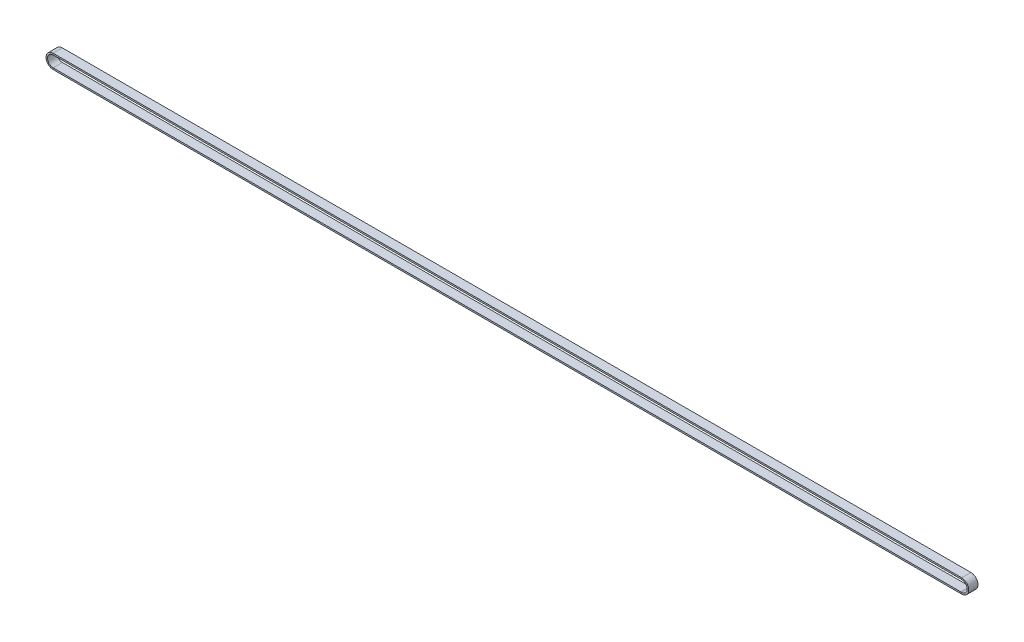
SolidWorks part; units mm, degrees
ref_plane "Front Plane" through (0, 0, 0) normal (0, 0, 1) x (1, 0, 0)
ref_plane "Top Plane" through (0, 0, 0) normal (0, 1, 0) x (1, 0, 0)
ref_plane "Right Plane" through (0, 0, 0) normal (1, 0, 0) x (0, 0, -1)
sketch "Sketch2" plane through (0, 0, 0) normal (0, 0, 1) x (1, 0, 0)
  line L0 (0, 0) -> (1, 0) construction
  line L1 (0, 0) -> (0, 1) construction
  line L2 (1, -48.0181) -> (-883.5206, -48.0181)
  line L3 (-883.5206, -34.2181) -> (1, -34.2181)
  arc A0 (1, -34.2181) -> (1, -48.0181) centre (1, -41.1181) cw
  arc A1 (-883.5206, -48.0181) -> (-883.5206, -34.2181) centre (-883.5206, -41.1181) cw
sketch "Sketch3" plane through (0, 0, 0) normal (1, 0, 0) x (0, 0, -1)
  line L1 (0, -46.5181) -> (-9, -46.5181)
  line L2 (0, -46.5181) -> (0, -48.0181)
  line L3 (0, -48.0181) -> (-9, -48.0181)
  line L4 (-9, -46.5181) -> (-9, -48.0181)
  point P4 (0, -46.9786)
  dimension "D1" = 9
  dimension "D2" = 1.5
sweep "Sweep1" add profiles "Sketch3" path "Sketch2"
